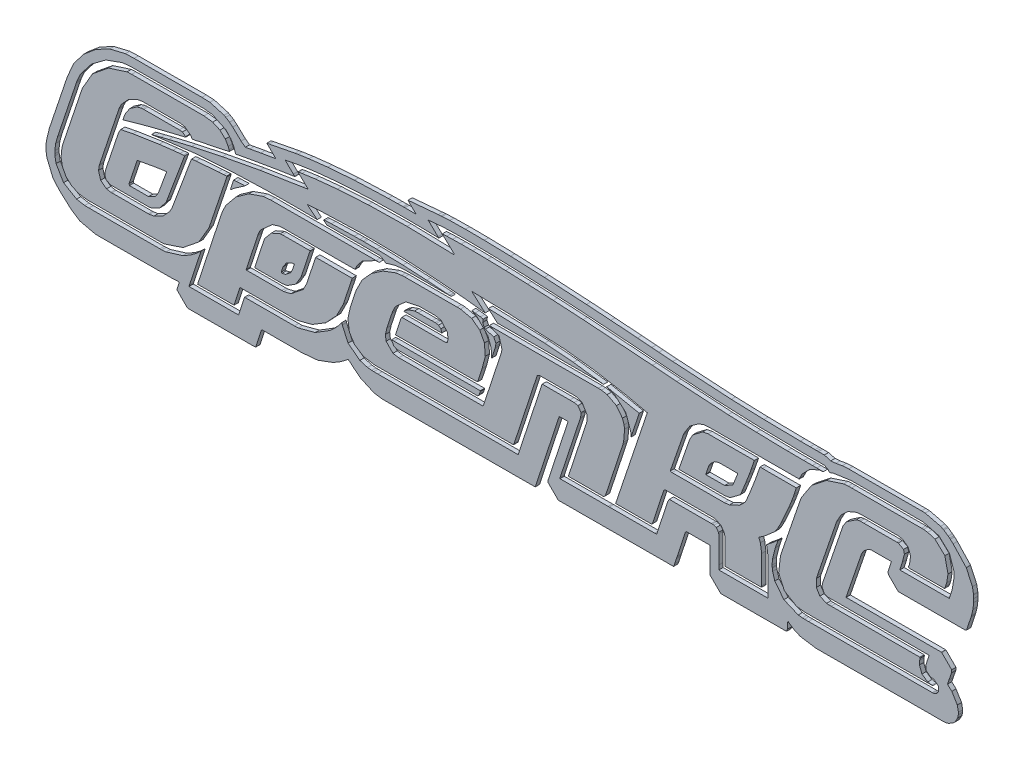
SolidWorks part; units mm, degrees
ref_plane "Plan de face" through (0, 0, 0) normal (0, 0, 1) x (1, 0, 0)
ref_plane "Plan de dessus" through (0, 0, 0) normal (0, 1, 0) x (1, 0, 0)
ref_plane "Plan de droite" through (0, 0, 0) normal (1, 0, 0) x (0, 0, -1)
sketch "Esquisse1" plane through (0, 0, 0) normal (0, 0, 1) x (1, 0, 0)
  line L709 (38.6595, 10.359) -> (34.1759, 10.3484)
  line L710 (33.872, 12.4667) -> (30.7956, 12.4595)
  line L711 (41.0982, 11.164) -> (41.1031, 11.4889)
  line L712 (41.0312, 10.5877) -> (41.0982, 11.164)
  line L713 (40.8956, 10.0124) -> (41.0312, 10.5877)
  line L714 (40.864, 9.908) -> (40.8956, 10.0124)
  line L715 (40.8469, 9.8566) -> (40.864, 9.908)
  line L716 (40.4313, 8.6012) -> (40.8469, 9.8566)
  line L717 (40.3423, 8.5357) -> (40.4313, 8.6012)
  line L718 (34.1148, 8.5211) -> (40.3423, 8.5357)
  line L719 (34.0248, 8.5231) -> (34.1148, 8.5211)
  line L720 (33.1261, 9.4177) -> (34.0248, 8.5231)
  line L721 (33.0562, 9.6241) -> (33.1261, 9.4177)
  line L722 (33.3872, 10.6334) -> (33.0562, 9.6241)
  line L723 (33.2701, 10.6381) -> (33.3872, 10.6334)
  line L724 (31.563, 10.6341) -> (33.2701, 10.6381)
  line L725 (31.5089, 10.6332) -> (31.563, 10.6341)
  line L726 (31.4263, 10.6238) -> (31.5089, 10.6332)
  line L727 (31.2202, 10.5531) -> (31.4263, 10.6238)
  line L728 (30.7741, 10.1926) -> (31.2202, 10.5531)
  line L729 (30.5929, 9.8756) -> (30.7741, 10.1926)
  line L730 (30.5912, 9.8702) -> (30.5929, 9.8756)
  line L731 (30.5042, 9.6159) -> (30.5912, 9.8702)
  line L732 (29.1559, 5.6763) -> (30.5042, 9.6159)
  line L733 (29.1396, 5.6023) -> (29.1559, 5.6763)
  line L734 (38.083, 5.6232) -> (29.1396, 5.6023)
  line L735 (38.1079, 5.6042) -> (38.083, 5.6232)
  line L736 (39.0365, 4.6799) -> (38.1079, 5.6042)
  line L737 (39.0259, 4.429) -> (39.0365, 4.6799)
  line L738 (38.7781, 3.7159) -> (39.0259, 4.429)
  line L739 (38.6415, 3.305) -> (38.7781, 3.7159)
  line L740 (39.0491, 2.9341) -> (38.6415, 3.305)
  line L741 (39.5621, 2.0812) -> (39.0491, 2.9341)
  line L742 (39.6694, 1.5491) -> (39.5621, 2.0812)
  line L743 (39.6624, 1.3466) -> (39.6694, 1.5491)
  line L744 (39.5886, 1.0226) -> (39.6624, 1.3466)
  line L745 (39.3686, 0.6253) -> (39.5886, 1.0226)
  line L746 (39.2431, 0.4862) -> (39.3686, 0.6253)
  line L747 (38.7535, 0.1768) -> (39.2431, 0.4862)
  line L748 (38.4417, 0.0999) -> (38.7535, 0.1768)
  line L749 (38.3234, 0.0898) -> (38.4417, 0.0999)
  line L750 (38.263, 0.0885) -> (38.3234, 0.0898)
  line L751 (26.2997, 0.0605) -> (38.263, 0.0885)
  line L752 (24.8443, 0.2906) -> (26.2997, 0.0605)
  line L753 (24.285, 0.5409) -> (24.8443, 0.2906)
  line L754 (23.9842, 0.7243) -> (24.285, 0.5409)
  line L755 (23.7023, 0.9346) -> (23.9842, 0.7243)
  line L756 (23.6402, 0.7894) -> (23.7023, 0.9346)
  line L757 (23.6414, 0.2753) -> (23.6402, 0.7894)
  line L758 (23.5536, 0.054) -> (23.6414, 0.2753)
  line L759 (17.4547, 0.0397) -> (23.5536, 0.054)
  line L760 (17.3868, 0.0436) -> (17.4547, 0.0397)
  line L761 (16.7151, 0.7121) -> (17.3868, 0.0436)
  line L762 (16.3861, 1.0397) -> (16.7151, 0.7121)
  line L763 (16.3804, 3.4533) -> (16.3861, 1.0397)
  line L764 (16.2169, 3.459) -> (16.3804, 3.4533)
  line L765 (14.1322, 3.4541) -> (16.2169, 3.459)
  line L766 (14.0684, 3.3375) -> (14.1322, 3.4541)
  line L767 (13.3125, 1.0315) -> (14.0684, 3.3375)
  line L768 (13.2914, 0.9673) -> (13.3125, 1.0315)
  line L769 (13.2903, 0.9646) -> (13.2914, 0.9673)
  line L770 (13.2386, 0.8076) -> (13.2903, 0.9646)
  line L771 (13.0717, 0.2991) -> (13.2386, 0.8076)
  line L772 (12.9703, 0.0296) -> (13.0717, 0.2991)
  line L773 (8.4624, 0.0188) -> (12.9703, 0.0296)
  line L774 (8.3937, 0.0185) -> (8.4624, 0.0188)
  line L775 (2.2451, 0.004) -> (8.3937, 0.0185)
  line L776 (2.1176, 0.0468) -> (2.2451, 0.004)
  line L777 (1.1851, 0.975) -> (2.1176, 0.0468)
  line L778 (1.2018, 1.1426) -> (1.1851, 0.975)
  line L779 (3.0717, 6.8266) -> (1.2018, 1.1426)
  line L780 (3.0716, 6.8513) -> (3.0717, 6.8266)
  line L781 (2.3093, 6.8495) -> (3.0716, 6.8513)
  line L782 (2.2424, 6.8364) -> (2.3093, 6.8495)
  line L783 (0, 0) -> (2.2424, 6.8364)
  line L784 (-0.3141, -0.002) -> (0, 0)
  line L785 (-14.0057, -0.0341) -> (-0.3141, -0.002)
  line L786 (-14.3727, -0.0261) -> (-14.0057, -0.0341)
  line L787 (-15.1174, 0.0811) -> (-14.3727, -0.0261)
  line L788 (-16.4017, 0.6659) -> (-15.1174, 0.0811)
  line L789 (-17.0455, 1.1752) -> (-16.4017, 0.6659)
  line L790 (-17.3583, 1.4577) -> (-17.0455, 1.1752)
  line L791 (-17.5544, 1.5817) -> (-17.3583, 1.4577)
  line L792 (-17.8869, 1.3057) -> (-17.5544, 1.5817)
  line L793 (-18.3355, 0.9869) -> (-17.8869, 1.3057)
  line L794 (-18.9749, 0.6173) -> (-18.3355, 0.9869)
  line L795 (-20.3843, 0.0964) -> (-18.9749, 0.6173)
  line L796 (-21.8897, -0.0384) -> (-20.3843, 0.0964)
  line L797 (-25.6208, -0.0472) -> (-21.8897, -0.0384)
  line L798 (-25.6793, -0.1471) -> (-25.6208, -0.0472)
  line L799 (-26.192, -1.736) -> (-25.6793, -0.1471)
  line L800 (-26.4297, -1.7678) -> (-26.192, -1.736)
  line L801 (-32.3677, -1.7818) -> (-26.4297, -1.7678)
  line L802 (-32.6136, -1.7641) -> (-32.3677, -1.7818)
  line L803 (-33.3307, -1.0503) -> (-32.6136, -1.7641)
  line L804 (-33.5984, -0.7775) -> (-33.3307, -1.0503)
  line L805 (-33.3713, -0.086) -> (-33.5984, -0.7775)
  line L806 (-33.5077, -0.0429) -> (-33.3713, -0.086)
  line L807 (-33.8035, -0.0708) -> (-33.5077, -0.0429)
  line L808 (-34.1006, -0.0812) -> (-33.8035, -0.0708)
  line L809 (-34.2315, -0.0816) -> (-34.1006, -0.0812)
  line L810 (-40.9062, -0.0972) -> (-34.2315, -0.0816)
  line L811 (-41.2364, -0.0905) -> (-40.9062, -0.0972)
  line L812 (-42.6942, 0.2518) -> (-41.2364, -0.0905)
  line L813 (-43.5098, 0.7892) -> (-42.6942, 0.2518)
  line L814 (-44.5314, 1.7075) -> (-43.5098, 0.7892)
  line L815 (-44.9334, 2.1359) -> (-44.5314, 1.7075)
  line L816 (-45.0978, 2.3462) -> (-44.9334, 2.1359)
  line L817 (-45.0992, 2.3486) -> (-45.0978, 2.3462)
  line L818 (-45.1299, 2.3893) -> (-45.0992, 2.3486)
  line L819 (-45.2288, 2.5267) -> (-45.1299, 2.3893)
  line L820 (-45.7783, 3.8454) -> (-45.2288, 2.5267)
  line L821 (-45.8338, 4.1978) -> (-45.7783, 3.8454)
  line L822 (-45.8457, 4.3135) -> (-45.8338, 4.1978)
  line L823 (-45.8566, 4.4724) -> (-45.8457, 4.3135)
  line L824 (-45.8609, 4.6309) -> (-45.8566, 4.4724)
  line L825 (-45.8322, 5.1569) -> (-45.8609, 4.6309)
  line L826 (-45.5504, 6.3298) -> (-45.8322, 5.1569)
  line L827 (-43.8665, 11.3607) -> (-45.5504, 6.3298)
  line L828 (-43.2557, 12.7587) -> (-43.8665, 11.3607)
  line L829 (-42.337, 13.9569) -> (-43.2557, 12.7587)
  line L830 (-41.2037, 14.9192) -> (-42.337, 13.9569)
  line L831 (-39.8807, 15.6125) -> (-41.2037, 14.9192)
  line L832 (-38.412, 15.9668) -> (-39.8807, 15.6125)
  line L833 (-37.5972, 15.9931) -> (-38.412, 15.9668)
  line L834 (-31.2426, 16.008) -> (-37.5972, 15.9931)
  line L835 (-30.4997, 15.978) -> (-31.2426, 16.008)
  line L836 (-29.1764, 15.5935) -> (-30.4997, 15.978)
  line L837 (-29.0084, 15.5039) -> (-29.1764, 15.5935)
  line L838 (-28.6671, 15.2841) -> (-29.0084, 15.5039)
  line L839 (-28.3627, 15.0371) -> (-28.6671, 15.2841)
  line L840 (-27.5709, 14.2862) -> (-28.3627, 15.0371)
  line L841 (-27.1775, 13.9888) -> (-27.5709, 14.2862)
  line L842 (-26.7547, 14.0644) -> (-27.1775, 13.9888)
  line L843 (-25.7261, 14.2466) -> (-26.7547, 14.0644)
  line L844 (-24.3127, 14.4878) -> (-25.7261, 14.2466)
  line L845 (-25.1643, 15.3249) -> (-24.3127, 14.4878)
  line L846 (-24.9295, 15.3706) -> (-25.1643, 15.3249)
  line L847 (-22.5295, 15.8349) -> (-24.9295, 15.3706)
  line L848 (-22.2434, 15.8857) -> (-22.5295, 15.8349)
  line L849 (-21.2143, 16.0372) -> (-22.2434, 15.8857)
  line L850 (-19.4435, 16.2358) -> (-21.2143, 16.0372)
  line L851 (-16.9558, 16.4232) -> (-19.4435, 16.2358)
  line L852 (-13.7757, 16.5413) -> (-16.9558, 16.4232)
  line L853 (-12.8753, 16.5532) -> (-13.7757, 16.5413)
  line L854 (-12.4096, 16.5558) -> (-12.8753, 16.5532)
  line L855 (-12.3144, 16.5561) -> (-12.4096, 16.5558)
  line L856 (-12.2019, 16.5562) -> (-12.3144, 16.5561)
  line L857 (-11.2814, 16.5525) -> (-12.2019, 16.5562)
  line L858 (-11.1642, 16.5664) -> (-11.2814, 16.5525)
  line L859 (-11.7393, 17.1124) -> (-11.1642, 16.5664)
  line L860 (-11.9267, 17.3144) -> (-11.7393, 17.1124)
  line L861 (-9.0928, 17.5644) -> (-11.9267, 17.3144)
  line L862 (-8.8354, 17.5871) -> (-9.0928, 17.5644)
  line L863 (-8.7236, 17.5953) -> (-8.8354, 17.5871)
  line L864 (-8.0079, 17.6283) -> (-8.7236, 17.5953)
  line L865 (-6.542, 17.6519) -> (-8.0079, 17.6283)
  line L866 (-4.7738, 17.6393) -> (-6.542, 17.6519)
  line L867 (-2.3138, 17.5767) -> (-4.7738, 17.6393)
  line L868 (0.8558, 17.4436) -> (-2.3138, 17.5767)
  line L869 (4.8011, 17.2199) -> (0.8558, 17.4436)
  line L870 (7.0851, 17.0678) -> (4.8011, 17.2199)
  line L871 (9.5878, 16.8854) -> (7.0851, 17.0678)
  line L872 (10.9236, 16.7821) -> (9.5878, 16.8854)
  line L873 (11.5839, 16.7304) -> (10.9236, 16.7821)
  line L874 (12.8925, 16.6314) -> (11.5839, 16.7304)
  line L875 (18.379, 16.3017) -> (12.8925, 16.6314)
  line L876 (21.4423, 16.1963) -> (18.379, 16.3017)
  line L877 (24.8476, 16.1454) -> (21.4423, 16.1963)
  line L878 (25.7637, 16.1424) -> (24.8476, 16.1454)
  line L879 (26.2324, 16.1426) -> (25.7637, 16.1424)
  line L880 (26.4195, 16.1429) -> (26.2324, 16.1426)
  line L881 (26.5551, 16.1433) -> (26.4195, 16.1429)
  line L882 (27.0973, 16.1428) -> (26.5551, 16.1433)
  line L883 (27.7056, 15.974) -> (27.0973, 16.1428)
  line L884 (28.1766, 16.0096) -> (27.7056, 15.974)
  line L885 (28.7803, 16.115) -> (28.1766, 16.0096)
  line L886 (29.3755, 16.1503) -> (28.7803, 16.115)
  line L887 (36.2087, 16.1663) -> (29.3755, 16.1503)
  line L888 (36.552, 16.1561) -> (36.2087, 16.1663)
  line L889 (37.9935, 15.8032) -> (36.552, 16.1561)
  line L890 (38.2186, 15.6896) -> (37.9935, 15.8032)
  line L891 (38.2957, 15.6472) -> (38.2186, 15.6896)
  line L892 (38.7063, 15.3701) -> (38.2957, 15.6472)
  line L893 (38.8396, 15.2616) -> (38.7063, 15.3701)
  line L894 (38.9043, 15.2049) -> (38.8396, 15.2616)
  line L895 (39.1677, 14.9701) -> (38.9043, 15.2049)
  line L896 (40.4035, 13.6539) -> (39.1677, 14.9701)
  line L897 (40.9817, 12.3993) -> (40.4035, 13.6539)
  line L898 (41.0828, 11.8197) -> (40.9817, 12.3993)
  line L899 (41.0844, 11.8025) -> (41.0828, 11.8197)
  line L900 (41.0865, 11.7744) -> (41.0844, 11.8025)
  line L901 (41.1031, 11.4889) -> (41.0865, 11.7744)
  line L902 (39.2743, 12.3819) -> (39.2582, 12.7233)
  line L903 (39.2582, 12.7233) -> (39.2572, 12.7359)
  line L904 (39.2572, 12.7359) -> (38.8391, 14.01)
  line L905 (38.8391, 14.01) -> (37.8253, 14.9648)
  line L906 (37.8253, 14.9648) -> (36.3728, 15.3388)
  line L907 (36.3728, 15.3388) -> (36.2029, 15.3411)
  line L908 (36.2029, 15.3411) -> (29.6026, 15.3256)
  line L909 (29.6026, 15.3256) -> (27.948, 15.0892)
  line L910 (27.948, 15.0892) -> (27.7264, 15.0104)
  line L911 (27.7264, 15.0104) -> (27.6842, 14.9931)
  line L912 (27.6842, 14.9931) -> (27.6003, 14.9571)
  line L913 (27.6003, 14.9571) -> (27.4716, 15.1217)
  line L914 (27.4716, 15.1217) -> (27.1123, 15.3138)
  line L915 (27.1123, 15.3138) -> (26.4776, 15.3177)
  line L916 (26.4776, 15.3177) -> (26.4211, 15.3176)
  line L917 (26.4211, 15.3176) -> (25.2856, 15.3181)
  line L918 (25.2856, 15.3181) -> (20.9357, 15.3842)
  line L919 (20.9357, 15.3842) -> (17.1166, 15.5362)
  line L920 (17.1166, 15.5362) -> (13.6334, 15.7508)
  line L921 (13.6334, 15.7508) -> (11.9567, 15.8742)
  line L922 (11.9567, 15.8742) -> (11.1239, 15.9386)
  line L923 (11.1239, 15.9386) -> (10.5305, 15.9852)
  line L924 (10.5305, 15.9852) -> (9.6842, 16.0505)
  line L925 (9.6842, 16.0505) -> (6.5266, 16.2793)
  line L926 (6.5266, 16.2793) -> (3.7207, 16.4599)
  line L927 (3.7207, 16.4599) -> (1.2495, 16.5977)
  line L928 (1.2495, 16.5977) -> (-0.9038, 16.6978)
  line L929 (-0.9038, 16.6978) -> (-2.7561, 16.7654)
  line L930 (-2.7561, 16.7654) -> (-4.3244, 16.8059)
  line L931 (-4.3244, 16.8059) -> (-5.6254, 16.8243)
  line L932 (-5.6254, 16.8243) -> (-6.5953, 16.8263)
  line L933 (-6.5953, 16.8263) -> (-7.5904, 16.8139)
  line L934 (-7.5904, 16.8139) -> (-8.2637, 16.7931)
  line L935 (-8.2637, 16.7931) -> (-8.6466, 16.7734)
  line L936 (-8.6466, 16.7734) -> (-8.9822, 16.7457)
  line L937 (-8.9822, 16.7457) -> (-10.0552, 16.651)
  line L938 (-10.0552, 16.651) -> (-9.9172, 16.5199)
  line L939 (-9.9172, 16.5199) -> (-9.1205, 15.7638)
  line L940 (-9.1205, 15.7638) -> (-9.1193, 15.7627)
  line L941 (-9.1193, 15.7627) -> (-9.0521, 15.6989)
  line L942 (-9.0521, 15.6989) -> (-9.0347, 15.6823)
  line L943 (-9.0347, 15.6823) -> (-9.2873, 15.6894)
  line L944 (-9.2873, 15.6894) -> (-9.7133, 15.7008)
  line L945 (-9.7133, 15.7008) -> (-11.3513, 15.7279)
  line L946 (-11.3513, 15.7279) -> (-12.1304, 15.7311)
  line L947 (-12.1304, 15.7311) -> (-12.321, 15.7309)
  line L948 (-12.321, 15.7309) -> (-13.405, 15.722)
  line L949 (-13.405, 15.722) -> (-15.5302, 15.6657)
  line L950 (-15.5302, 15.6657) -> (-17.3802, 15.5709)
  line L951 (-17.3802, 15.5709) -> (-18.9486, 15.4524)
  line L952 (-18.9486, 15.4524) -> (-20.2291, 15.3253)
  line L953 (-20.2291, 15.3253) -> (-21.2152, 15.2045)
  line L954 (-21.2152, 15.2045) -> (-21.9006, 15.1051)
  line L955 (-21.9006, 15.1051) -> (-22.2788, 15.0421)
  line L956 (-22.2788, 15.0421) -> (-22.4359, 15.0124)
  line L957 (-22.4359, 15.0124) -> (-23.4239, 14.8214)
  line L958 (-23.4239, 14.8214) -> (-23.4057, 14.7696)
  line L959 (-23.4057, 14.7696) -> (-22.6832, 14.0697)
  line L960 (-22.6832, 14.0697) -> (-22.6542, 14.0417)
  line L961 (-22.6542, 14.0417) -> (-22.6525, 14.0397)
  line L962 (-22.6525, 14.0397) -> (-22.5747, 13.9642)
  line L963 (-22.5747, 13.9642) -> (-22.5357, 13.9265)
  line L964 (-22.5357, 13.9265) -> (-22.9289, 13.8675)
  line L965 (-22.9289, 13.8675) -> (-24.7059, 13.5847)
  line L966 (-24.7059, 13.5847) -> (-26.2074, 13.3231)
  line L967 (-26.2074, 13.3231) -> (-27.2501, 13.1375)
  line L968 (-27.2501, 13.1375) -> (-28.0897, 12.983)
  line L969 (-28.0897, 12.983) -> (-28.0935, 12.999)
  line L970 (-28.0935, 12.999) -> (-28.1094, 13.0635)
  line L971 (-28.1094, 13.0635) -> (-28.2696, 13.5287)
  line L972 (-28.2696, 13.5287) -> (-28.5177, 13.9738)
  line L973 (-28.5177, 13.9738) -> (-28.9884, 14.491)
  line L974 (-28.9884, 14.491) -> (-30.2923, 15.1103)
  line L975 (-30.2923, 15.1103) -> (-31.0588, 15.1832)
  line L976 (-31.0588, 15.1832) -> (-37.9063, 15.1672)
  line L977 (-37.9063, 15.1672) -> (-38.7011, 15.0934)
  line L978 (-38.7011, 15.0934) -> (-40.2544, 14.5326)
  line L979 (-40.2544, 14.5326) -> (-41.591, 13.5381)
  line L980 (-41.591, 13.5381) -> (-42.6204, 12.2087)
  line L981 (-42.6204, 12.2087) -> (-42.9664, 11.4475)
  line L982 (-42.9664, 11.4475) -> (-43.0198, 11.2909)
  line L983 (-43.0198, 11.2909) -> (-44.7825, 6.0246)
  line L984 (-44.7825, 6.0246) -> (-44.9591, 5.3952)
  line L985 (-44.9591, 5.3952) -> (-45.0338, 4.7808)
  line L986 (-45.0338, 4.7808) -> (-45.0332, 4.5291)
  line L987 (-45.0332, 4.5291) -> (-45.0224, 4.3699)
  line L988 (-45.0224, 4.3699) -> (-44.9163, 3.7905)
  line L989 (-44.9163, 3.7905) -> (-44.2168, 2.5923)
  line L990 (-44.2168, 2.5923) -> (-42.993, 1.8673)
  line L991 (-42.993, 1.8673) -> (-42.2346, 1.7354)
  line L992 (-42.2346, 1.7354) -> (-41.8371, 1.7277)
  line L993 (-41.8371, 1.7277) -> (-35.1857, 1.7433)
  line L994 (-35.1857, 1.7433) -> (-35.013, 1.7451)
  line L995 (-35.013, 1.7451) -> (-34.6089, 1.7756)
  line L996 (-34.6089, 1.7756) -> (-33.0413, 2.2573)
  line L997 (-33.0413, 2.2573) -> (-32.3256, 2.6659)
  line L998 (-32.3256, 2.6659) -> (-31.825, 3.0345)
  line L999 (-31.825, 3.0345) -> (-31.4789, 3.3417)
  line L1000 (-31.4789, 3.3417) -> (-31.3286, 3.4878)
  line L1001 (-31.3286, 3.4878) -> (-32.415, 0.1801)
  line L1002 (-32.415, 0.1801) -> (-32.4591, 0.045)
  line L1003 (-32.4591, 0.045) -> (-27.8098, 0.0559)
  line L1004 (-27.8098, 0.0559) -> (-27.7307, 0.2951)
  line L1005 (-27.7307, 0.2951) -> (-27.2542, 1.7724)
  line L1006 (-27.2542, 1.7724) -> (-27.132, 1.7765)
  line L1007 (-27.132, 1.7765) -> (-22.5743, 1.7872)
  line L1008 (-22.5743, 1.7872) -> (-22.2145, 1.8009)
  line L1009 (-22.2145, 1.8009) -> (-20.6254, 2.2228)
  line L1010 (-20.6254, 2.2228) -> (-19.2218, 3.0974)
  line L1011 (-19.2218, 3.0974) -> (-18.6181, 3.6734)
  line L1012 (-18.6181, 3.6734) -> (-18.345, 3.9926)
  line L1013 (-18.345, 3.9926) -> (-18.2285, 4.1434)
  line L1014 (-18.2285, 4.1434) -> (-18.1636, 4.2366)
  line L1015 (-18.1636, 4.2366) -> (-18.1316, 4.2835)
  line L1016 (-18.1316, 4.2835) -> (-18.087, 4.1112)
  line L1017 (-18.087, 4.1112) -> (-17.5493, 2.9021)
  line L1018 (-17.5493, 2.9021) -> (-16.4414, 2.0529)
  line L1019 (-16.4414, 2.0529) -> (-15.7177, 1.8407)
  line L1020 (-15.7177, 1.8407) -> (-15.3292, 1.7974)
  line L1021 (-15.3292, 1.7974) -> (-15.1293, 1.7907)
  line L1022 (-15.1293, 1.7907) -> (-14.7481, 1.7913)
  line L1023 (-14.7481, 1.7913) -> (-1.6823, 1.822)
  line L1024 (-1.6823, 1.822) -> (-1.6009, 1.8291)
  line L1025 (-1.6009, 1.8291) -> (-1.4722, 2.2208)
  line L1026 (-1.4722, 2.2208) -> (-1.4583, 2.2631)
  line L1027 (-1.4583, 2.2631) -> (0.5939, 8.5201)
  line L1028 (0.5939, 8.5201) -> (0.6527, 8.6732)
  line L1029 (0.6527, 8.6732) -> (3.2415, 8.679)
  line L1030 (3.2415, 8.679) -> (3.6539, 8.6798)
  line L1031 (3.6539, 8.6798) -> (4.0013, 8.6092)
  line L1032 (4.0013, 8.6092) -> (4.2954, 8.1825)
  line L1033 (4.2954, 8.1825) -> (4.3001, 8.1001)
  line L1034 (4.3001, 8.1001) -> (4.2467, 7.7605)
  line L1035 (4.2467, 7.7605) -> (4.2184, 7.6723)
  line L1036 (4.2184, 7.6723) -> (2.3308, 1.9338)
  line L1037 (2.3308, 1.9338) -> (2.3244, 1.8314)
  line L1038 (2.3244, 1.8314) -> (6.8311, 1.8419)
  line L1039 (6.8311, 1.8419) -> (6.9462, 1.8426)
  line L1040 (6.9462, 1.8426) -> (6.9486, 1.8426)
  line L1041 (6.9486, 1.8426) -> (11.1902, 1.8526)
  line L1042 (11.1902, 1.8526) -> (11.386, 1.869)
  line L1043 (11.386, 1.869) -> (11.5036, 2.2275)
  line L1044 (11.5036, 2.2275) -> (11.5119, 2.2518)
  line L1045 (11.5119, 2.2518) -> (11.5347, 2.3212)
  line L1046 (11.5347, 2.3212) -> (12.4263, 5.0403)
  line L1047 (12.4263, 5.0403) -> (12.5677, 5.2778)
  line L1048 (12.5677, 5.2778) -> (16.5058, 5.2871)
  line L1049 (16.5058, 5.2871) -> (16.5972, 5.2862)
  line L1050 (16.5972, 5.2862) -> (16.7523, 5.271)
  line L1051 (16.7523, 5.271) -> (16.9664, 5.1927)
  line L1052 (16.9664, 5.1927) -> (17.1841, 4.9009)
  line L1053 (17.1841, 4.9009) -> (17.2027, 4.7945)
  line L1054 (17.2027, 4.7945) -> (17.2086, 2.2744)
  line L1055 (17.2086, 2.2744) -> (17.2114, 1.8663)
  line L1056 (17.2114, 1.8663) -> (21.8103, 1.8771)
  line L1057 (21.8103, 1.8771) -> (21.8102, 2.0084)
  line L1058 (21.8102, 2.0084) -> (21.8026, 5.2214)
  line L1059 (21.8026, 5.2214) -> (21.7954, 5.4472)
  line L1060 (21.7954, 5.4472) -> (21.7324, 5.9161)
  line L1061 (21.7324, 5.9161) -> (21.6762, 6.1424)
  line L1062 (21.6762, 6.1424) -> (21.916, 6.3437)
  line L1063 (21.916, 6.3437) -> (22.4636, 6.7908)
  line L1064 (22.4636, 6.7908) -> (22.72, 7.0399)
  line L1065 (22.72, 7.0399) -> (22.7367, 6.9918)
  line L1066 (22.7367, 6.9918) -> (22.5033, 6.3098)
  line L1067 (22.5033, 6.3098) -> (22.2288, 5.22)
  line L1068 (22.2288, 5.22) -> (22.206, 4.7601)
  line L1069 (22.206, 4.7601) -> (22.213, 4.6001)
  line L1070 (22.213, 4.6001) -> (22.2197, 4.5203)
  line L1071 (22.2197, 4.5203) -> (22.2524, 4.2708)
  line L1072 (22.2524, 4.2708) -> (22.4535, 3.5878)
  line L1073 (22.4535, 3.5878) -> (23.3079, 2.5034)
  line L1074 (23.3079, 2.5034) -> (24.6493, 1.9334)
  line L1075 (24.6493, 1.9334) -> (25.0384, 1.8914)
  line L1076 (25.0384, 1.8914) -> (25.2385, 1.8853)
  line L1077 (25.2385, 1.8853) -> (25.6196, 1.886)
  line L1078 (25.6196, 1.886) -> (37.2116, 1.9132)
  line L1079 (37.2116, 1.9132) -> (37.2709, 1.9135)
  line L1080 (37.2709, 1.9135) -> (37.3332, 1.9182)
  line L1081 (37.3332, 1.9182) -> (37.5076, 1.9693)
  line L1082 (37.5076, 1.9693) -> (37.7071, 2.1244)
  line L1083 (37.7071, 2.1244) -> (37.8155, 2.3258)
  line L1084 (37.8155, 2.3258) -> (37.7955, 2.7195)
  line L1085 (37.7955, 2.7195) -> (37.3779, 3.0652)
  line L1086 (37.3779, 3.0652) -> (37.0485, 3.0955)
  line L1087 (37.0485, 3.0955) -> (36.6445, 3.4157)
  line L1088 (36.6445, 3.4157) -> (36.6013, 3.7899)
  line L1089 (36.6013, 3.7899) -> (36.738, 4.2485)
  line L1090 (36.738, 4.2485) -> (36.9275, 4.7939)
  line L1091 (36.9275, 4.7939) -> (36.677, 4.7948)
  line L1092 (36.677, 4.7948) -> (27.5901, 4.7734)
  line L1093 (27.5901, 4.7734) -> (27.5026, 4.7738)
  line L1094 (27.5026, 4.7738) -> (27.3916, 4.7821)
  line L1095 (27.3916, 4.7821) -> (27.0968, 4.8899)
  line L1096 (27.0968, 4.8899) -> (26.8912, 5.3048)
  line L1097 (26.8912, 5.3048) -> (26.8929, 5.4436)
  line L1098 (26.8929, 5.4436) -> (26.9228, 5.6191)
  line L1099 (26.9228, 5.6191) -> (26.95, 5.7143)
  line L1100 (26.95, 5.7143) -> (28.8026, 11.1268)
  line L1101 (28.8026, 11.1268) -> (28.848, 11.2522)
  line L1102 (28.848, 11.2522) -> (29.1515, 11.7396)
  line L1103 (29.1515, 11.7396) -> (30.11, 12.395)
  line L1104 (30.11, 12.395) -> (30.3633, 12.4487)
  line L1105 (30.3633, 12.4487) -> (30.489, 12.4582)
  line L1106 (30.489, 12.4582) -> (30.7956, 12.4595)
  line L1107 (30.7956, 12.4595) -> (33.872, 12.4667)
  line L1108 (33.872, 12.4667) -> (34.0211, 12.4647)
  line L1109 (34.0211, 12.4647) -> (34.5264, 12.1935)
  line L1110 (34.5264, 12.1935) -> (34.6035, 11.8399)
  line L1111 (34.6035, 11.8399) -> (34.4133, 11.1136)
  line L1112 (34.4133, 11.1136) -> (34.4114, 11.1072)
  line L1113 (34.4114, 11.1072) -> (34.1759, 10.3484)
  line L1114 (34.1759, 10.3484) -> (38.6595, 10.359)
  line L1115 (38.6595, 10.359) -> (38.809, 10.3599)
  line L1116 (38.809, 10.3599) -> (39.0734, 11.1584)
  line L1117 (39.0734, 11.1584) -> (39.2743, 12.3819)
  line L1118 (36.4076, 14.7542) -> (36.7905, 14.7125)
  line L1119 (36.7905, 14.7125) -> (37.4655, 14.4958)
  line L1120 (37.4655, 14.4958) -> (38.3959, 13.6145)
  line L1121 (38.3959, 13.6145) -> (38.6905, 12.2783)
  line L1122 (38.6905, 12.2783) -> (38.5659, 11.4959)
  line L1123 (38.5659, 11.4959) -> (38.4607, 11.1594)
  line L1124 (38.4607, 11.1594) -> (38.3663, 10.9402)
  line L1125 (38.3663, 10.9402) -> (35.0383, 10.9324)
  line L1126 (35.0383, 10.9324) -> (34.9809, 10.9751)
  line L1127 (34.9809, 10.9751) -> (35.0821, 11.2839)
  line L1128 (35.0821, 11.2839) -> (35.1834, 11.9574)
  line L1129 (35.1834, 11.9574) -> (34.9594, 12.5917)
  line L1130 (34.9594, 12.5917) -> (34.4254, 12.975)
  line L1131 (34.4254, 12.975) -> (34.0661, 13.0449)
  line L1132 (34.0661, 13.0449) -> (33.8186, 13.0483)
  line L1133 (33.8186, 13.0483) -> (30.5283, 13.0406)
  line L1134 (30.5283, 13.0406) -> (30.1195, 12.9976)
  line L1135 (30.1195, 12.9976) -> (29.3204, 12.6601)
  line L1136 (29.3204, 12.6601) -> (28.6608, 12.0589)
  line L1137 (28.6608, 12.0589) -> (28.2475, 11.3014)
  line L1138 (28.2475, 11.3014) -> (26.4496, 6.0489)
  line L1139 (26.4496, 6.0489) -> (26.3592, 5.7626)
  line L1140 (26.3592, 5.7626) -> (26.3481, 5.0225)
  line L1141 (26.3481, 5.0225) -> (26.6786, 4.4786)
  line L1142 (26.6786, 4.4786) -> (27.3072, 4.2059)
  line L1143 (27.3072, 4.2059) -> (27.5061, 4.1912)
  line L1144 (27.5061, 4.1912) -> (27.7405, 4.1913)
  line L1145 (27.7405, 4.1913) -> (36.063, 4.2108)
  line L1146 (36.063, 4.2108) -> (36.0854, 4.1377)
  line L1147 (36.0854, 4.1377) -> (36.036, 3.9355)
  line L1148 (36.036, 3.9355) -> (36.0178, 3.5593)
  line L1149 (36.0178, 3.5593) -> (36.25, 2.9382)
  line L1150 (36.25, 2.9382) -> (36.7868, 2.5627)
  line L1151 (36.7868, 2.5627) -> (37.1583, 2.4978)
  line L1152 (37.1583, 2.4978) -> (37.258, 2.4954)
  line L1153 (37.258, 2.4954) -> (25.3834, 2.4676)
  line L1154 (25.3834, 2.4676) -> (25.2502, 2.4673)
  line L1155 (25.2502, 2.4673) -> (24.4901, 2.5614)
  line L1156 (24.4901, 2.5614) -> (23.3528, 3.2499)
  line L1157 (23.3528, 3.2499) -> (22.8161, 4.4348)
  line L1158 (22.8161, 4.4348) -> (22.9941, 5.9452)
  line L1159 (22.9941, 5.9452) -> (24.8039, 11.2323)
  line L1160 (24.8039, 11.2323) -> (24.9447, 11.6165)
  line L1161 (24.9447, 11.6165) -> (25.9143, 13.0903)
  line L1162 (25.9143, 13.0903) -> (27.3063, 14.1786)
  line L1163 (27.3063, 14.1786) -> (28.9311, 14.7154)
  line L1164 (28.9311, 14.7154) -> (29.343, 14.7422)
  line L1165 (29.343, 14.7422) -> (29.6532, 14.7431)
  line L1166 (29.6532, 14.7431) -> (36.2188, 14.7585)
  line L1167 (36.2188, 14.7585) -> (36.4076, 14.7542)
  line L1168 (21.0621, 12.1523) -> (21.2965, 12.153)
  line L1169 (21.2965, 12.153) -> (24.4707, 12.1604)
  line L1170 (24.4707, 12.1604) -> (24.2634, 11.5227)
  line L1171 (24.2634, 11.5227) -> (24.1885, 11.2927)
  line L1172 (24.1885, 11.2927) -> (24.0146, 10.8246)
  line L1173 (24.0146, 10.8246) -> (23.7394, 10.1465)
  line L1174 (23.7394, 10.1465) -> (23.0515, 8.6148)
  line L1175 (23.0515, 8.6148) -> (22.7222, 7.9887)
  line L1176 (22.7222, 7.9887) -> (22.458, 7.6059)
  line L1177 (22.458, 7.6059) -> (21.4604, 6.735)
  line L1178 (21.4604, 6.735) -> (20.9513, 6.3996)
  line L1179 (20.9513, 6.3996) -> (21.1039, 6.0252)
  line L1180 (21.1039, 6.0252) -> (21.2206, 5.2159)
  line L1181 (21.2206, 5.2159) -> (21.2268, 2.5839)
  line L1182 (21.2268, 2.5839) -> (21.2117, 2.4578)
  line L1183 (21.2117, 2.4578) -> (17.9294, 2.4501)
  line L1184 (17.9294, 2.4501) -> (17.7904, 2.465)
  line L1185 (17.7904, 2.465) -> (17.785, 4.7533)
  line L1186 (17.785, 4.7533) -> (17.7793, 4.8882)
  line L1187 (17.7793, 4.8882) -> (17.7075, 5.1718)
  line L1188 (17.7075, 5.1718) -> (17.3709, 5.6197)
  line L1189 (17.3709, 5.6197) -> (16.8207, 5.8497)
  line L1190 (16.8207, 5.8497) -> (16.4897, 5.8691)
  line L1191 (16.4897, 5.8691) -> (12.1843, 5.859)
  line L1192 (12.1843, 5.859) -> (12.063, 5.7993)
  line L1193 (12.063, 5.7993) -> (10.9806, 2.4991)
  line L1194 (10.9806, 2.4991) -> (10.8876, 2.4336)
  line L1195 (10.8876, 2.4336) -> (7.5901, 2.4258)
  line L1196 (7.5901, 2.4258) -> (7.5372, 2.4282)
  line L1197 (7.5372, 2.4282) -> (10.5027, 11.275)
  line L1198 (10.5027, 11.275) -> (10.1596, 11.3588)
  line L1199 (10.1596, 11.3588) -> (8.5689, 11.715)
  line L1200 (8.5689, 11.715) -> (5.5971, 12.2399)
  line L1201 (5.5971, 12.2399) -> (2.8355, 12.5622)
  line L1202 (2.8355, 12.5622) -> (-2.39, 12.8277)
  line L1203 (-2.39, 12.8277) -> (-5.0203, 12.8852)
  line L1204 (-5.0203, 12.8852) -> (-5.6938, 12.9014)
  line L1205 (-5.6938, 12.9014) -> (-5.9624, 12.9084)
  line L1206 (-5.9624, 12.9084) -> (-4.6959, 11.778)
  line L1207 (-4.6959, 11.778) -> (-4.7135, 11.7732)
  line L1208 (-4.7135, 11.7732) -> (-5.0148, 11.8122)
  line L1209 (-5.0148, 11.8122) -> (-5.6266, 11.8852)
  line L1210 (-5.6266, 11.8852) -> (-6.5196, 11.9816)
  line L1211 (-6.5196, 11.9816) -> (-7.6649, 12.091)
  line L1212 (-7.6649, 12.091) -> (-9.0333, 12.2026)
  line L1213 (-9.0333, 12.2026) -> (-12.3231, 12.3906)
  line L1214 (-12.3231, 12.3906) -> (-16.1563, 12.461)
  line L1215 (-16.1563, 12.461) -> (-20.3003, 12.3293)
  line L1216 (-20.3003, 12.3293) -> (-21.3575, 12.2548)
  line L1217 (-21.3575, 12.2548) -> (-21.3775, 12.2491)
  line L1218 (-21.3775, 12.2491) -> (-20.4398, 11.4856)
  line L1219 (-20.4398, 11.4856) -> (-20.4992, 11.4845)
  line L1220 (-20.4992, 11.4845) -> (-20.8843, 11.4933)
  line L1221 (-20.8843, 11.4933) -> (-21.5852, 11.5041)
  line L1222 (-21.5852, 11.5041) -> (-22.5615, 11.5109)
  line L1223 (-22.5615, 11.5109) -> (-25.1789, 11.4887)
  line L1224 (-25.1789, 11.4887) -> (-28.4136, 11.3785)
  line L1225 (-28.4136, 11.3785) -> (-31.9428, 11.1324)
  line L1226 (-31.9428, 11.1324) -> (-35.4437, 10.7022)
  line L1227 (-35.4437, 10.7022) -> (-35.8632, 10.6331)
  line L1228 (-35.8632, 10.6331) -> (-35.9849, 10.6125)
  line L1229 (-35.9849, 10.6125) -> (-35.9302, 10.6276)
  line L1230 (-35.9302, 10.6276) -> (-35.6335, 10.7072)
  line L1231 (-35.6335, 10.7072) -> (-35.0984, 10.8462)
  line L1232 (-35.0984, 10.8462) -> (-34.3383, 11.0365)
  line L1233 (-34.3383, 11.0365) -> (-32.1971, 11.5393)
  line L1234 (-32.1971, 11.5393) -> (-29.3177, 12.1515)
  line L1235 (-29.3177, 12.1515) -> (-25.808, 12.8092)
  line L1236 (-25.808, 12.8092) -> (-21.7758, 13.4483)
  line L1237 (-21.7758, 13.4483) -> (-21.278, 13.5185)
  line L1238 (-21.278, 13.5185) -> (-22.2457, 14.4557)
  line L1239 (-22.2457, 14.4557) -> (-22.1641, 14.4711)
  line L1240 (-22.1641, 14.4711) -> (-21.8646, 14.5213)
  line L1241 (-21.8646, 14.5213) -> (-20.622, 14.6933)
  line L1242 (-20.622, 14.6933) -> (-18.5464, 14.9021)
  line L1243 (-18.5464, 14.9021) -> (-15.6679, 15.0773)
  line L1244 (-15.6679, 15.0773) -> (-12.0167, 15.1484)
  line L1245 (-12.0167, 15.1484) -> (-7.6228, 15.0452)
  line L1246 (-7.6228, 15.0452) -> (-7.5988, 15.1224)
  line L1247 (-7.5988, 15.1224) -> (-8.6317, 16.1021)
  line L1248 (-8.6317, 16.1021) -> (-8.7183, 16.1844)
  line L1249 (-8.7183, 16.1844) -> (-8.2958, 16.2087)
  line L1250 (-8.2958, 16.2087) -> (-7.7471, 16.2275)
  line L1251 (-7.7471, 16.2275) -> (-6.9433, 16.2413)
  line L1252 (-6.9433, 16.2413) -> (-5.8621, 16.2432)
  line L1253 (-5.8621, 16.2432) -> (-4.481, 16.2262)
  line L1254 (-4.481, 16.2262) -> (-2.7773, 16.1833)
  line L1255 (-2.7773, 16.1833) -> (-0.7288, 16.1074)
  line L1256 (-0.7288, 16.1074) -> (1.6871, 15.9917)
  line L1257 (1.6871, 15.9917) -> (4.4929, 15.8292)
  line L1258 (4.4929, 15.8292) -> (10.9861, 15.3655)
  line L1259 (10.9861, 15.3655) -> (13.2706, 15.1929)
  line L1260 (13.2706, 15.1929) -> (18.0796, 14.9066)
  line L1261 (18.0796, 14.9066) -> (20.7266, 14.8078)
  line L1262 (20.7266, 14.8078) -> (23.6168, 14.7487)
  line L1263 (23.6168, 14.7487) -> (25.1724, 14.7364)
  line L1264 (25.1724, 14.7364) -> (25.9811, 14.7349)
  line L1265 (25.9811, 14.7349) -> (26.3936, 14.7354)
  line L1266 (26.3936, 14.7354) -> (27.0023, 14.7368)
  line L1267 (27.0023, 14.7368) -> (26.6514, 14.6985)
  line L1268 (26.6514, 14.6985) -> (25.7308, 14.294)
  line L1269 (25.7308, 14.294) -> (25.0123, 13.552)
  line L1270 (25.0123, 13.552) -> (24.7879, 13.103)
  line L1271 (24.7879, 13.103) -> (24.7539, 13.0187)
  line L1272 (24.7539, 13.0187) -> (24.7486, 13.0134)
  line L1273 (24.7486, 13.0134) -> (24.6401, 13.0127)
  line L1274 (24.6401, 13.0127) -> (16.4099, 12.9934)
  line L1275 (16.4099, 12.9934) -> (15.7925, 12.9476)
  line L1276 (15.7925, 12.9476) -> (15.3185, 12.7856)
  line L1277 (15.3185, 12.7856) -> (14.491, 12.1898)
  line L1278 (14.491, 12.1898) -> (13.9416, 11.3269)
  line L1279 (13.9416, 11.3269) -> (13.8856, 11.1684)
  line L1280 (13.8856, 11.1684) -> (12.6486, 7.6107)
  line L1281 (12.6486, 7.6107) -> (12.8199, 7.5791)
  line L1282 (12.8199, 7.5791) -> (17.7316, 7.5906)
  line L1283 (17.7316, 7.5906) -> (18.2061, 7.6434)
  line L1284 (18.2061, 7.6434) -> (19.127, 8.0753)
  line L1285 (19.127, 8.0753) -> (19.5104, 8.4203)
  line L1286 (19.5104, 8.4203) -> (19.6786, 8.6211)
  line L1287 (19.6786, 8.6211) -> (19.797, 8.8408)
  line L1288 (19.797, 8.8408) -> (19.9954, 9.2997)
  line L1289 (19.9954, 9.2997) -> (20.4689, 10.4903)
  line L1290 (20.4689, 10.4903) -> (20.6606, 10.9948)
  line L1291 (20.6606, 10.9948) -> (20.7666, 11.2871)
  line L1292 (20.7666, 11.2871) -> (20.9825, 11.9193)
  line L1293 (20.9825, 11.9193) -> (21.0621, 12.1523)
  line L1294 (14.4751, 11.0923) -> (14.7521, 11.598)
  line L1295 (14.7521, 11.598) -> (15.6982, 12.3141)
  line L1296 (15.6982, 12.3141) -> (16.1995, 12.4112)
  line L1297 (16.1995, 12.4112) -> (20.5386, 12.4212)
  line L1298 (20.5386, 12.4212) -> (20.2196, 11.4878)
  line L1299 (20.2196, 11.4878) -> (20.0491, 11.0238)
  line L1300 (20.0491, 11.0238) -> (19.7198, 10.1732)
  line L1301 (19.7198, 10.1732) -> (19.3792, 9.3364)
  line L1302 (19.3792, 9.3364) -> (19.2522, 9.0505)
  line L1303 (19.2522, 9.0505) -> (19.2124, 8.9703)
  line L1304 (19.2124, 8.9703) -> (18.2753, 8.2714)
  line L1305 (18.2753, 8.2714) -> (17.7628, 8.173)
  line L1306 (17.7628, 8.173) -> (13.4567, 8.1629)
  line L1307 (13.4567, 8.1629) -> (14.4751, 11.0923)
  line L1308 (9.7485, 10.858) -> (8.967, 8.5271)
  line L1309 (8.967, 8.5271) -> (8.9708, 8.6177)
  line L1310 (8.9708, 8.6177) -> (8.9537, 8.9508)
  line L1311 (8.9537, 8.9508) -> (8.9533, 8.9525)
  line L1312 (8.9533, 8.9525) -> (8.4852, 10.2961)
  line L1313 (8.4852, 10.2961) -> (7.4259, 11.2213)
  line L1314 (7.4259, 11.2213) -> (6.6909, 11.4771)
  line L1315 (6.6909, 11.4771) -> (9.7485, 10.858)
  line L1316 (3.568, 11.9045) -> (6.4016, 11.5242)
  line L1317 (6.4016, 11.5242) -> (5.9167, 11.5535)
  line L1318 (5.9167, 11.5535) -> (-3.5446, 11.5313)
  line L1319 (-3.5446, 11.5313) -> (-4.3945, 12.2895)
  line L1320 (-4.3945, 12.2895) -> (0.8843, 12.1194)
  line L1321 (0.8843, 12.1194) -> (3.568, 11.9045)
  line L1322 (-5.4734, 11.1052) -> (-5.9559, 11.3311)
  line L1323 (-5.9559, 11.3311) -> (-5.6449, 11.3017)
  line L1324 (-5.6449, 11.3017) -> (-5.1387, 11.2413)
  line L1325 (-5.1387, 11.2413) -> (-4.8754, 11.1914)
  line L1326 (-4.8754, 11.1914) -> (-4.9298, 10.8932)
  line L1327 (-4.9298, 10.8932) -> (-4.7835, 10.5588)
  line L1328 (-4.7835, 10.5588) -> (-4.6717, 10.462)
  line L1329 (-4.6717, 10.462) -> (-3.8894, 10.2373)
  line L1330 (-3.8894, 10.2373) -> (-3.6955, 9.8086)
  line L1331 (-3.6955, 9.8086) -> (-3.7126, 9.5804)
  line L1332 (-3.7126, 9.5804) -> (-3.7637, 9.3852)
  line L1333 (-3.7637, 9.3852) -> (-4.0817, 8.4177)
  line L1334 (-4.0817, 8.4177) -> (-4.0912, 8.4163)
  line L1335 (-4.0912, 8.4163) -> (-4.0875, 8.5274)
  line L1336 (-4.0875, 8.5274) -> (-4.0968, 8.8441)
  line L1337 (-4.0968, 8.8441) -> (-4.1066, 8.9494)
  line L1338 (-4.1066, 8.9494) -> (-4.1717, 9.3333)
  line L1339 (-4.1717, 9.3333) -> (-4.4362, 10.0419)
  line L1340 (-4.4362, 10.0419) -> (-5.4734, 11.1052)
  line L1341 (8.1706, 9.669) -> (8.3231, 9.2103)
  line L1342 (8.3231, 9.2103) -> (8.3746, 8.8919)
  line L1343 (8.3746, 8.8919) -> (8.2793, 7.7801)
  line L1344 (8.2793, 7.7801) -> (8.2024, 7.5155)
  line L1345 (8.2024, 7.5155) -> (6.5736, 2.5715)
  line L1346 (6.5736, 2.5715) -> (6.4109, 2.423)
  line L1347 (6.4109, 2.423) -> (3.124, 2.4153)
  line L1348 (3.124, 2.4153) -> (3.1189, 2.4662)
  line L1349 (3.1189, 2.4662) -> (4.749, 7.4226)
  line L1350 (4.749, 7.4226) -> (4.796, 7.5657)
  line L1351 (4.796, 7.5657) -> (4.8361, 7.7114)
  line L1352 (4.8361, 7.7114) -> (4.8725, 8.263)
  line L1353 (4.8725, 8.263) -> (4.3861, 9.0583)
  line L1354 (4.3861, 9.0583) -> (3.9147, 9.2404)
  line L1355 (3.9147, 9.2404) -> (3.6424, 9.2617)
  line L1356 (3.6424, 9.2617) -> (0.4061, 9.2541)
  line L1357 (0.4061, 9.2541) -> (0.1903, 9.1569)
  line L1358 (0.1903, 9.1569) -> (-1.978, 2.5463)
  line L1359 (-1.978, 2.5463) -> (-2.0397, 2.4032)
  line L1360 (-2.0397, 2.4032) -> (-15.0451, 2.3727)
  line L1361 (-15.0451, 2.3727) -> (-16.121, 2.55)
  line L1362 (-16.121, 2.55) -> (-16.9311, 3.0794)
  line L1363 (-16.9311, 3.0794) -> (-17.4261, 3.874)
  line L1364 (-17.4261, 3.874) -> (-17.562, 4.8932)
  line L1365 (-17.562, 4.8932) -> (-17.3293, 5.9483)
  line L1366 (-17.3293, 5.9483) -> (-16.8615, 7.3629)
  line L1367 (-16.8615, 7.3629) -> (-16.7989, 7.5538)
  line L1368 (-16.7989, 7.5538) -> (-16.2321, 8.6834)
  line L1369 (-16.2321, 8.6834) -> (-15.361, 9.6487)
  line L1370 (-15.361, 9.6487) -> (-14.2965, 10.3792)
  line L1371 (-14.2965, 10.3792) -> (-13.1126, 10.8309)
  line L1372 (-13.1126, 10.8309) -> (-12.5116, 10.92)
  line L1373 (-12.5116, 10.92) -> (-12.2439, 10.9286)
  line L1374 (-12.2439, 10.9286) -> (-7.3345, 10.9402)
  line L1375 (-7.3345, 10.9402) -> (-7.0078, 10.9385)
  line L1376 (-7.0078, 10.9385) -> (-5.9629, 10.7049)
  line L1377 (-5.9629, 10.7049) -> (-5.2016, 10.1353)
  line L1378 (-5.2016, 10.1353) -> (-4.7658, 9.308)
  line L1379 (-4.7658, 9.308) -> (-4.6858, 8.2664)
  line L1380 (-4.6858, 8.2664) -> (-4.9727, 7.1387)
  line L1381 (-4.9727, 7.1387) -> (-5.4046, 5.8326)
  line L1382 (-5.4046, 5.8326) -> (-5.4671, 5.8176)
  line L1383 (-5.4671, 5.8176) -> (-13.107, 5.7996)
  line L1384 (-13.107, 5.7996) -> (-12.5755, 7.4067)
  line L1385 (-12.5755, 7.4067) -> (-12.5012, 7.5197)
  line L1386 (-12.5012, 7.5197) -> (-8.3867, 7.5293)
  line L1387 (-8.3867, 7.5293) -> (-8.2408, 7.6056)
  line L1388 (-8.2408, 7.6056) -> (-8.1849, 7.8909)
  line L1389 (-8.1849, 7.8909) -> (-8.2204, 8.4172)
  line L1390 (-8.2204, 8.4172) -> (-8.8253, 9.1159)
  line L1391 (-8.8253, 9.1159) -> (-9.3482, 9.2301)
  line L1392 (-9.3482, 9.2301) -> (-9.4782, 9.2309)
  line L1393 (-9.4782, 9.2309) -> (-10.8627, 9.2277)
  line L1394 (-10.8627, 9.2277) -> (-12.1385, 8.9571)
  line L1395 (-12.1385, 8.9571) -> (-13.0999, 8.1027)
  line L1396 (-13.0999, 8.1027) -> (-13.3832, 7.5394)
  line L1397 (-13.3832, 7.5394) -> (-13.4388, 7.3709)
  line L1398 (-13.4388, 7.3709) -> (-13.9066, 5.9564)
  line L1399 (-13.9066, 5.9564) -> (-14.0447, 5.3541)
  line L1400 (-14.0447, 5.3541) -> (-13.9814, 4.8407)
  line L1401 (-13.9814, 4.8407) -> (-13.3355, 4.1824)
  line L1402 (-13.3355, 4.1824) -> (-12.7867, 4.0962)
  line L1403 (-12.7867, 4.0962) -> (-4.8916, 4.1147)
  line L1404 (-4.8916, 4.1147) -> (-4.8475, 4.2217)
  line L1405 (-4.8475, 4.2217) -> (-3.2242, 9.1623)
  line L1406 (-3.2242, 9.1623) -> (-3.172, 9.3321)
  line L1407 (-3.172, 9.3321) -> (-3.1199, 9.6159)
  line L1408 (-3.1199, 9.6159) -> (-3.3857, 10.5597)
  line L1409 (-3.3857, 10.5597) -> (-4.3067, 10.9468)
  line L1410 (-4.3067, 10.9468) -> (-4.2948, 10.9473)
  line L1411 (-4.2948, 10.9473) -> (5.916, 10.9713)
  line L1412 (5.916, 10.9713) -> (6.1998, 10.9607)
  line L1413 (6.1998, 10.9607) -> (6.7378, 10.8671)
  line L1414 (6.7378, 10.8671) -> (7.6111, 10.407)
  line L1415 (7.6111, 10.407) -> (8.1706, 9.669)
  line L1416 (-8.7607, 8.1368) -> (-8.7595, 8.1202)
  line L1417 (-8.7595, 8.1202) -> (-8.7589, 8.1117)
  line L1418 (-8.7589, 8.1117) -> (-8.878, 8.1104)
  line L1419 (-8.878, 8.1104) -> (-12.3155, 8.1024)
  line L1420 (-12.3155, 8.1024) -> (-12.3214, 8.1183)
  line L1421 (-12.3214, 8.1183) -> (-12.2696, 8.1652)
  line L1422 (-12.2696, 8.1652) -> (-11.8995, 8.4248)
  line L1423 (-11.8995, 8.4248) -> (-11.3111, 8.6317)
  line L1424 (-11.3111, 8.6317) -> (-10.9712, 8.6455)
  line L1425 (-10.9712, 8.6455) -> (-9.68, 8.6486)
  line L1426 (-9.68, 8.6486) -> (-9.3967, 8.6491)
  line L1427 (-9.3967, 8.6491) -> (-9.2745, 8.6412)
  line L1428 (-9.2745, 8.6412) -> (-9.0803, 8.5921)
  line L1429 (-9.0803, 8.5921) -> (-8.8476, 8.4133)
  line L1430 (-8.8476, 8.4133) -> (-8.7607, 8.1368)
  line L1431 (-12.9822, 4.6899) -> (-13.244, 4.7857)
  line L1432 (-13.244, 4.7857) -> (-13.4617, 5.1868)
  line L1433 (-13.4617, 5.1868) -> (-13.4631, 5.2133)
  line L1434 (-13.4631, 5.2133) -> (-13.4633, 5.2166)
  line L1435 (-13.4633, 5.2166) -> (-13.2573, 5.2176)
  line L1436 (-13.2573, 5.2176) -> (-5.151, 5.2366)
  line L1437 (-5.151, 5.2366) -> (-5.1435, 5.1868)
  line L1438 (-5.1435, 5.1868) -> (-5.2484, 4.8672)
  line L1439 (-5.2484, 4.8672) -> (-5.3889, 4.696)
  line L1440 (-5.3889, 4.696) -> (-12.7266, 4.6784)
  line L1441 (-12.7266, 4.6784) -> (-12.9822, 4.6899)
  line L1442 (-14.1167, 11.2357) -> (-14.1889, 11.3281)
  line L1443 (-14.1889, 11.3281) -> (-14.5656, 11.5038)
  line L1444 (-14.5656, 11.5038) -> (-14.5898, 11.5051)
  line L1445 (-14.5898, 11.5051) -> (-14.6019, 11.5053)
  line L1446 (-14.6019, 11.5053) -> (-14.608, 11.5054)
  line L1447 (-14.608, 11.5054) -> (-19.5138, 11.4939)
  line L1448 (-19.5138, 11.4939) -> (-19.5812, 11.5372)
  line L1449 (-19.5812, 11.5372) -> (-19.8373, 11.7458)
  line L1450 (-19.8373, 11.7458) -> (-19.6577, 11.7824)
  line L1451 (-19.6577, 11.7824) -> (-19.1098, 11.8086)
  line L1452 (-19.1098, 11.8086) -> (-16.9653, 11.8718)
  line L1453 (-16.9653, 11.8718) -> (-16.427, 11.8777)
  line L1454 (-16.427, 11.8777) -> (-16.1597, 11.8792)
  line L1455 (-16.1597, 11.8792) -> (-16.0265, 11.8797)
  line L1456 (-16.0265, 11.8797) -> (-14.8642, 11.8744)
  line L1457 (-14.8642, 11.8744) -> (-12.4088, 11.8118)
  line L1458 (-12.4088, 11.8118) -> (-10.1828, 11.6983)
  line L1459 (-10.1828, 11.6983) -> (-8.2523, 11.5575)
  line L1460 (-8.2523, 11.5575) -> (-8.0498, 11.5404)
  line L1461 (-8.0498, 11.5404) -> (-8.0335, 11.539)
  line L1462 (-8.0335, 11.539) -> (-8.001, 11.5362)
  line L1463 (-8.001, 11.5362) -> (-7.8731, 11.525)
  line L1464 (-7.8731, 11.525) -> (-7.9403, 11.521)
  line L1465 (-7.9403, 11.521) -> (-12.2183, 11.511)
  line L1466 (-12.2183, 11.511) -> (-13.0893, 11.4308)
  line L1467 (-13.0893, 11.4308) -> (-13.9099, 11.1936)
  line L1468 (-13.9099, 11.1936) -> (-14.0026, 11.1544)
  line L1469 (-14.0026, 11.1544) -> (-14.1167, 11.2357)
  line L1470 (-17.1676, 8.3606) -> (-17.2549, 8.0672)
  line L1471 (-17.2549, 8.0672) -> (-17.9946, 5.8309)
  line L1472 (-17.9946, 5.8309) -> (-18.6268, 4.5841)
  line L1473 (-18.6268, 4.5841) -> (-19.6492, 3.4994)
  line L1474 (-19.6492, 3.4994) -> (-20.9059, 2.7349)
  line L1475 (-20.9059, 2.7349) -> (-22.283, 2.3793)
  line L1476 (-22.283, 2.3793) -> (-22.5945, 2.369)
  line L1477 (-22.5945, 2.369) -> (-27.54, 2.3574)
  line L1478 (-27.54, 2.3574) -> (-27.6781, 2.3543)
  line L1479 (-27.6781, 2.3543) -> (-28.2318, 0.6375)
  line L1480 (-28.2318, 0.6375) -> (-28.3537, 0.6369)
  line L1481 (-28.3537, 0.6369) -> (-31.6393, 0.6292)
  line L1482 (-31.6393, 0.6292) -> (-31.6117, 0.7597)
  line L1483 (-31.6117, 0.7597) -> (-29.4392, 7.3738)
  line L1484 (-29.4392, 7.3738) -> (-29.3194, 7.7125)
  line L1485 (-29.3194, 7.7125) -> (-28.9957, 8.3663)
  line L1486 (-28.9957, 8.3663) -> (-28.0516, 9.5194)
  line L1487 (-28.0516, 9.5194) -> (-26.8478, 10.3702)
  line L1488 (-26.8478, 10.3702) -> (-25.4846, 10.8455)
  line L1489 (-25.4846, 10.8455) -> (-24.7958, 10.8992)
  line L1490 (-24.7958, 10.8992) -> (-14.9255, 10.9224)
  line L1491 (-14.9255, 10.9224) -> (-14.6187, 10.923)
  line L1492 (-14.6187, 10.923) -> (-14.9688, 10.8895)
  line L1493 (-14.9688, 10.8895) -> (-16.2442, 10.1999)
  line L1494 (-16.2442, 10.1999) -> (-16.7043, 9.6131)
  line L1495 (-16.7043, 9.6131) -> (-16.8547, 9.289)
  line L1496 (-16.8547, 9.289) -> (-16.8833, 9.2136)
  line L1497 (-16.8833, 9.2136) -> (-23.704, 9.1976)
  line L1498 (-23.704, 9.1976) -> (-23.7855, 9.196)
  line L1499 (-23.7855, 9.196) -> (-23.9607, 9.1813)
  line L1500 (-23.9607, 9.1813) -> (-24.6486, 8.9701)
  line L1501 (-24.6486, 8.9701) -> (-25.7478, 7.9928)
  line L1502 (-25.7478, 7.9928) -> (-25.9171, 7.6712)
  line L1503 (-25.9171, 7.6712) -> (-25.9796, 7.5044)
  line L1504 (-25.9796, 7.5044) -> (-26.0149, 7.3964)
  line L1505 (-26.0149, 7.3964) -> (-27.0987, 4.0922)
  line L1506 (-27.0987, 4.0922) -> (-27.0651, 4.0627)
  line L1507 (-27.0651, 4.0627) -> (-23.7573, 4.0705)
  line L1508 (-23.7573, 4.0705) -> (-23.5765, 4.0741)
  line L1509 (-23.5765, 4.0741) -> (-22.8924, 4.2399)
  line L1510 (-22.8924, 4.2399) -> (-21.7452, 5.1616)
  line L1511 (-21.7452, 5.1616) -> (-21.4243, 5.8015)
  line L1512 (-21.4243, 5.8015) -> (-20.5805, 8.3526)
  line L1513 (-20.5805, 8.3526) -> (-17.1676, 8.3606)
  line L1514 (-23.9022, 8.6019) -> (-23.7028, 8.6157)
  line L1515 (-23.7028, 8.6157) -> (-21.2756, 8.6214)
  line L1516 (-21.2756, 8.6214) -> (-21.1048, 8.6212)
  line L1517 (-21.1048, 8.6212) -> (-21.1091, 8.6083)
  line L1518 (-21.1091, 8.6083) -> (-21.1426, 8.5069)
  line L1519 (-21.1426, 8.5069) -> (-21.9431, 6.087)
  line L1520 (-21.9431, 6.087) -> (-22.4413, 5.2431)
  line L1521 (-22.4413, 5.2431) -> (-23.2514, 4.7265)
  line L1522 (-23.2514, 4.7265) -> (-23.6574, 4.6533)
  line L1523 (-23.6574, 4.6533) -> (-23.828, 4.6526)
  line L1524 (-23.828, 4.6526) -> (-26.2876, 4.6468)
  line L1525 (-26.2876, 4.6468) -> (-26.2471, 4.8213)
  line L1526 (-26.2471, 4.8213) -> (-25.4345, 7.2992)
  line L1527 (-25.4345, 7.2992) -> (-25.3577, 7.4966)
  line L1528 (-25.3577, 7.4966) -> (-24.7438, 8.2333)
  line L1529 (-24.7438, 8.2333) -> (-23.9022, 8.6019)
  line L1530 (-28.2726, 10.7796) -> (-27.9994, 10.8014)
  line L1531 (-27.9994, 10.8014) -> (-27.208, 10.8363)
  line L1532 (-27.208, 10.8363) -> (-28.2924, 10.0858)
  line L1533 (-28.2924, 10.0858) -> (-28.5279, 9.8701)
  line L1534 (-28.5279, 9.8701) -> (-28.5624, 9.9187)
  line L1535 (-28.5624, 9.9187) -> (-28.3382, 10.5845)
  line L1536 (-28.3382, 10.5845) -> (-28.3038, 10.6869)
  line L1537 (-28.3038, 10.6869) -> (-28.2726, 10.7796)
  line L1538 (-28.9408, 10.7674) -> (-28.9086, 10.7139)
  line L1539 (-28.9086, 10.7139) -> (-30.5777, 5.7586)
  line L1540 (-30.5777, 5.7586) -> (-31.533, 4.1216)
  line L1541 (-31.533, 4.1216) -> (-33.0228, 2.9224)
  line L1542 (-33.0228, 2.9224) -> (-34.7681, 2.3434)
  line L1543 (-34.7681, 2.3434) -> (-35.2008, 2.3254)
  line L1544 (-35.2008, 2.3254) -> (-41.9691, 2.3095)
  line L1545 (-41.9691, 2.3095) -> (-42.7891, 2.4139)
  line L1546 (-42.7891, 2.4139) -> (-43.4654, 2.7264)
  line L1547 (-43.4654, 2.7264) -> (-43.9778, 3.1983)
  line L1548 (-43.9778, 3.1983) -> (-44.3127, 3.8109)
  line L1549 (-44.3127, 3.8109) -> (-44.4511, 4.5489)
  line L1550 (-44.4511, 4.5489) -> (-44.3675, 5.3758)
  line L1551 (-44.3675, 5.3758) -> (-44.2479, 5.7874)
  line L1552 (-44.2479, 5.7874) -> (-42.4524, 11.1515)
  line L1553 (-42.4524, 11.1515) -> (-41.4976, 12.7888)
  line L1554 (-41.4976, 12.7888) -> (-40.0178, 13.9982)
  line L1555 (-40.0178, 13.9982) -> (-38.2624, 14.5671)
  line L1556 (-38.2624, 14.5671) -> (-37.8293, 14.5847)
  line L1557 (-37.8293, 14.5847) -> (-31.0563, 14.6006)
  line L1558 (-31.0563, 14.6006) -> (-30.2364, 14.4987)
  line L1559 (-30.2364, 14.4987) -> (-29.5605, 14.1931)
  line L1560 (-29.5605, 14.1931) -> (-29.053, 13.7202)
  line L1561 (-29.053, 13.7202) -> (-28.7874, 13.2594)
  line L1562 (-28.7874, 13.2594) -> (-28.7024, 13.0231)
  line L1563 (-28.7024, 13.0231) -> (-28.6685, 12.8997)
  line L1564 (-28.6685, 12.8997) -> (-29.1489, 12.7788)
  line L1565 (-29.1489, 12.7788) -> (-31.3756, 12.3168)
  line L1566 (-31.3756, 12.3168) -> (-31.8753, 12.2076)
  line L1567 (-31.8753, 12.2076) -> (-32.1694, 12.1601)
  line L1568 (-32.1694, 12.1601) -> (-32.2028, 12.2403)
  line L1569 (-32.2028, 12.2403) -> (-32.2873, 12.3903)
  line L1570 (-32.2873, 12.3903) -> (-32.8524, 12.8172)
  line L1571 (-32.8524, 12.8172) -> (-33.2433, 12.8888)
  line L1572 (-33.2433, 12.8888) -> (-33.3391, 12.8907)
  line L1573 (-33.3391, 12.8907) -> (-36.7469, 12.8831)
  line L1574 (-36.7469, 12.8831) -> (-36.8474, 12.8807)
  line L1575 (-36.8474, 12.8807) -> (-37.2974, 12.8071)
  line L1576 (-37.2974, 12.8071) -> (-38.1385, 12.3769)
  line L1577 (-38.1385, 12.3769) -> (-38.7927, 11.6642)
  line L1578 (-38.7927, 11.6642) -> (-39.0001, 11.2463)
  line L1579 (-39.0001, 11.2463) -> (-39.0349, 11.1439)
  line L1580 (-39.0349, 11.1439) -> (-40.8404, 5.7501)
  line L1581 (-40.8404, 5.7501) -> (-40.8712, 5.6478)
  line L1582 (-40.8712, 5.6478) -> (-40.9336, 5.2302)
  line L1583 (-40.9336, 5.2302) -> (-40.745, 4.5267)
  line L1584 (-40.745, 4.5267) -> (-40.1861, 4.1064)
  line L1585 (-40.1861, 4.1064) -> (-39.7854, 4.0349)
  line L1586 (-39.7854, 4.0349) -> (-39.6863, 4.0331)
  line L1587 (-39.6863, 4.0331) -> (-36.2832, 4.0411)
  line L1588 (-36.2832, 4.0411) -> (-36.186, 4.0434)
  line L1589 (-36.186, 4.0434) -> (-35.7458, 4.1168)
  line L1590 (-35.7458, 4.1168) -> (-34.9056, 4.5404)
  line L1591 (-34.9056, 4.5404) -> (-34.2506, 5.2458)
  line L1592 (-34.2506, 5.2458) -> (-34.0333, 5.6638)
  line L1593 (-34.0333, 5.6638) -> (-33.9952, 5.7643)
  line L1594 (-33.9952, 5.7643) -> (-32.2223, 10.5071)
  line L1595 (-32.2223, 10.5071) -> (-31.7989, 10.5602)
  line L1596 (-31.7989, 10.5602) -> (-29.7125, 10.7213)
  line L1597 (-29.7125, 10.7213) -> (-29.197, 10.7528)
  line L1598 (-29.197, 10.7528) -> (-28.9408, 10.7674)
  line L1599 (-39.0728, 9.1975) -> (-38.8632, 9.5864)
  line L1600 (-38.8632, 9.5864) -> (-37.7111, 9.8153)
  line L1601 (-37.7111, 9.8153) -> (-35.2435, 10.1947)
  line L1602 (-35.2435, 10.1947) -> (-33.959, 10.3482)
  line L1603 (-33.959, 10.3482) -> (-33.3108, 10.4167)
  line L1604 (-33.3108, 10.4167) -> (-32.9861, 10.4489)
  line L1605 (-32.9861, 10.4489) -> (-32.866, 10.448)
  line L1606 (-32.866, 10.448) -> (-34.4351, 6.2502)
  line L1607 (-34.4351, 6.2502) -> (-34.555, 5.9289)
  line L1608 (-34.555, 5.9289) -> (-34.5998, 5.8197)
  line L1609 (-34.5998, 5.8197) -> (-35.1966, 5.0518)
  line L1610 (-35.1966, 5.0518) -> (-36.0313, 4.6471)
  line L1611 (-36.0313, 4.6471) -> (-36.23, 4.6242)
  line L1612 (-36.23, 4.6242) -> (-36.3888, 4.6229)
  line L1613 (-36.3888, 4.6229) -> (-39.638, 4.6157)
  line L1614 (-39.638, 4.6157) -> (-39.7596, 4.6168)
  line L1615 (-39.7596, 4.6168) -> (-40.225, 4.8034)
  line L1616 (-40.225, 4.8034) -> (-40.3505, 5.1528)
  line L1617 (-40.3505, 5.1528) -> (-40.2913, 5.557)
  line L1618 (-40.2913, 5.557) -> (-39.0728, 9.1975)
  line L1619 (-32.7479, 12.029) -> (-32.8668, 11.9826)
  line L1620 (-32.8668, 11.9826) -> (-34.1675, 11.6701)
  line L1621 (-34.1675, 11.6701) -> (-36.2982, 11.1337)
  line L1622 (-36.2982, 11.1337) -> (-38.0252, 10.6586)
  line L1623 (-38.0252, 10.6586) -> (-38.4532, 10.5328)
  line L1624 (-38.4532, 10.5328) -> (-38.6409, 10.488)
  line L1625 (-38.6409, 10.488) -> (-38.577, 10.6788)
  line L1626 (-38.577, 10.6788) -> (-38.4555, 11.0404)
  line L1627 (-38.4555, 11.0404) -> (-38.0129, 11.7116)
  line L1628 (-38.0129, 11.7116) -> (-37.3387, 12.1772)
  line L1629 (-37.3387, 12.1772) -> (-36.979, 12.2826)
  line L1630 (-36.979, 12.2826) -> (-36.8034, 12.3)
  line L1631 (-36.8034, 12.3) -> (-36.6959, 12.3011)
  line L1632 (-36.6959, 12.3011) -> (-33.3664, 12.3085)
  line L1633 (-33.3664, 12.3085) -> (-33.0807, 12.2789)
  line L1634 (-33.0807, 12.2789) -> (-32.7686, 12.0632)
  line L1635 (-32.7686, 12.0632) -> (-32.7479, 12.029)
  line L1636 (18.5127, 9.417) -> (17.7609, 8.9981)
  line L1637 (17.2082, 10.5862) -> (16.8326, 10.4684)
  line L1638 (16.8326, 10.4684) -> (16.4158, 10.1025)
  line L1639 (16.4158, 10.1025) -> (16.2849, 9.885)
  line L1640 (16.2849, 9.885) -> (16.2466, 9.7858)
  line L1641 (16.2466, 9.7858) -> (15.9836, 9.0295)
  line L1642 (15.9836, 9.0295) -> (15.9913, 8.994)
  line L1643 (15.9913, 8.994) -> (17.7609, 8.9981)
  line L1644 (17.7609, 8.9981) -> (18.5127, 9.417)
  line L1645 (18.5127, 9.417) -> (18.5884, 9.5862)
  line L1646 (18.5884, 9.5862) -> (18.7617, 10.0099)
  line L1647 (18.7617, 10.0099) -> (18.9302, 10.4355)
  line L1648 (18.9302, 10.4355) -> (18.9712, 10.5903)
  line L1649 (18.9712, 10.5903) -> (17.2082, 10.5862)
  line L1650 (-23.8137, 5.5307) -> (-23.7342, 5.4782)
  line L1651 (-23.7342, 5.4782) -> (-23.3994, 5.5543)
  line L1652 (-23.3994, 5.5543) -> (-22.9232, 5.9393)
  line L1653 (-22.9232, 5.9393) -> (-22.7639, 6.2323)
  line L1654 (-22.7639, 6.2323) -> (-22.718, 6.3714)
  line L1655 (-22.718, 6.3714) -> (-22.614, 6.6858)
  line L1656 (-22.614, 6.6858) -> (-22.5844, 6.7911)
  line L1657 (-22.5844, 6.7911) -> (-22.8669, 6.7674)
  line L1658 (-22.8669, 6.7674) -> (-23.3485, 6.4857)
  line L1659 (-23.3485, 6.4857) -> (-23.6434, 6.0499)
  line L1660 (-23.6434, 6.0499) -> (-23.8137, 5.5307)
  line L1661 (-38.0669, 5.6026) -> (-38.0409, 5.4444)
  line L1662 (-38.0409, 5.4444) -> (-36.2842, 5.4482)
  line L1663 (-36.2842, 5.4482) -> (-36.2345, 5.4506)
  line L1664 (-36.2345, 5.4506) -> (-35.6136, 5.7853)
  line L1665 (-35.6136, 5.7853) -> (-35.3516, 6.1606)
  line L1666 (-35.3516, 6.1606) -> (-35.3163, 6.2495)
  line L1667 (-35.3163, 6.2495) -> (-34.5752, 8.2323)
  line L1668 (-34.5752, 8.2323) -> (-34.5872, 8.3153)
  line L1669 (-34.5872, 8.3153) -> (-34.9932, 8.2579)
  line L1670 (-34.9932, 8.2579) -> (-35.7908, 8.1354)
  line L1671 (-35.7908, 8.1354) -> (-37.3117, 7.8586)
  line L1672 (-37.3117, 7.8586) -> (-38.0669, 5.6026)
extrude "Boss.-Extru.1" add sketch "Esquisse1" along normal blind 0.4 contours L711 L901 L900 L899 L898 L897 L896 L895 L894 L893 L892 L891 L890 L889 L888 L887 L886 L885 L884 L883 L882 L881 L880 L879 L878 L877 L876 L875 L874 L873 L872 L871 L870 L869 L868 L867 L866 L865 L864 L863 L862 L861 L860 L859 L858 L857 L856 L855 L854 L853 L852 | L1598 L1597 L1596 L1595 L1594 L1593 L1592 L1591 L1590 L1589 L1588 L1587 L1586 L1585 L1584 L1583 L1582 L1581 L1580 L1579 L1578 L1577 L1576 L1575 L1574 L1573 L1572 L1571 L1570 L1569 L1568 L1567 L1566 L1565 L1564 L1563 L1562 L1561 L1560 L1559 L1558 L1557 L1556 L1555 L1554 L1553 L1552 L1551 L1550 L1549 L1548 | L1618 L1617 L1616 L1615 L1614 L1613 L1612 L1611 L1610 L1609 L1608 L1607 L1606 L1605 L1604 L1603 L1602 L1601 L1600 L1599 L1672 L1671 L1670 L1669 L1668 L1667 L1666 L1665 L1664 L1663 L1662 L1661 | L1635 L1634 L1633 L1632 L1631 L1630 L1629 L1628 L1627 L1626 L1625 L1624 L1623 L1622 L1621 L1620 L1619 | L1293 L1292 L1291 L1290 L1289 L1288 L1287 L1286 L1285 L1284 L1283 L1282 L1281 L1280 L1279 L1278 L1277 L1276 L1275 L1274 L1273 L1272 L1271 L1270 L1269 L1268 L1267 L1266 L1265 L1264 L1263 L1262 L1261 L1260 L1259 L1258 L1257 L1256 L1255 L1254 L1253 L1252 L1251 L1250 L1249 L1248 L1247 L1246 L1245 L1244 L1243 | L1537 L1536 L1535 L1534 L1533 L1532 L1531 L1530 | L1513 L1512 L1511 L1510 L1509 L1508 L1507 L1506 L1505 L1504 L1503 L1502 L1501 L1500 L1499 L1498 L1497 L1496 L1495 L1494 L1493 L1492 L1491 L1490 L1489 L1488 L1487 L1486 L1485 L1484 L1483 L1482 L1481 L1480 L1479 L1478 L1477 L1476 L1475 L1474 L1473 L1472 L1471 L1470 | L1529 L1528 L1527 L1526 L1525 L1524 L1523 L1522 L1521 L1520 L1519 L1518 L1517 L1516 L1515 L1514 L1660 L1659 L1658 L1657 L1656 L1655 L1654 L1653 L1652 L1651 L1650 | L1469 L1468 L1467 L1466 L1465 L1464 L1463 L1462 L1461 L1460 L1459 L1458 L1457 L1456 L1455 L1454 L1453 L1452 L1451 L1450 L1449 L1448 L1447 L1446 L1445 L1444 L1443 L1442 | L1415 L1414 L1413 L1412 L1411 L1410 L1409 L1408 L1407 L1406 L1405 L1404 L1403 L1402 L1401 L1400 L1399 L1398 L1397 L1396 L1395 L1394 L1393 L1392 L1391 L1390 L1389 L1388 L1387 L1386 L1385 L1384 L1383 L1382 L1381 L1380 L1379 L1378 L1377 L1376 L1375 L1374 L1373 L1372 L1371 L1370 L1369 L1368 L1367 L1366 L1365 | L1430 L1429 L1428 L1427 L1426 L1425 L1424 L1423 L1422 L1421 L1420 L1419 L1418 L1417 L1416 | L1441 L1440 L1439 L1438 L1437 L1436 L1435 L1434 L1433 L1432 L1431 | L1340 L1339 L1338 L1337 L1336 L1335 L1334 L1333 L1332 L1331 L1330 L1329 L1328 L1327 L1326 L1325 L1324 L1323 L1322 | L1321 L1320 L1319 L1318 L1317 L1316 | L1315 L1314 L1313 L1312 L1311 L1310 L1309 L1308 | L1307 L1306 L1305 L1304 L1303 L1302 L1301 L1300 L1299 L1298 L1297 L1296 L1295 L1294 L1649 L1648 L1647 L1646 L1645 L1636 L1643 L1642 L1641 L1640 L1639 L1638 L1637 | L1167 L1166 L1165 L1164 L1163 L1162 L1161 L1160 L1159 L1158 L1157 L1156 L1155 L1154 L1153 L1152 L1151 L1150 L1149 L1148 L1147 L1146 L1145 L1144 L1143 L1142 L1141 L1140 L1139 L1138 L1137 L1136 L1135 L1134 L1133 L1132 L1131 L1130 L1129 L1128 L1127 L1126 L1125 L1124 L1123 L1122 L1121 L1120 L1119 L1118 region at (2.8769, 6.1677, 0) region at (36.5773, 14.5338, 0) region at (21.1812, 11.5078, 0) region at (14.6861, 11.3055, 0) region at (8.7901, 10.3753, 0) region at (-0.1109, 11.8355, 0) region at (-4.4052, 10.083, 0) region at (7.9876, 9.3534, 0) region at (-10.4143, 8.3544, 0) region at (-9.269, 4.9605, 0) region at (-14.7284, 11.6408, 0) region at (-17.4019, 8.2706, 0) region at (-23.7372, 6.6637, 0) region at (-28.0218, 10.4977, 0) region at (-29.0962, 10.6376, 0) region at (-38.8844, 9.347, 0) region at (-36.1157, 11.6661, 0)
